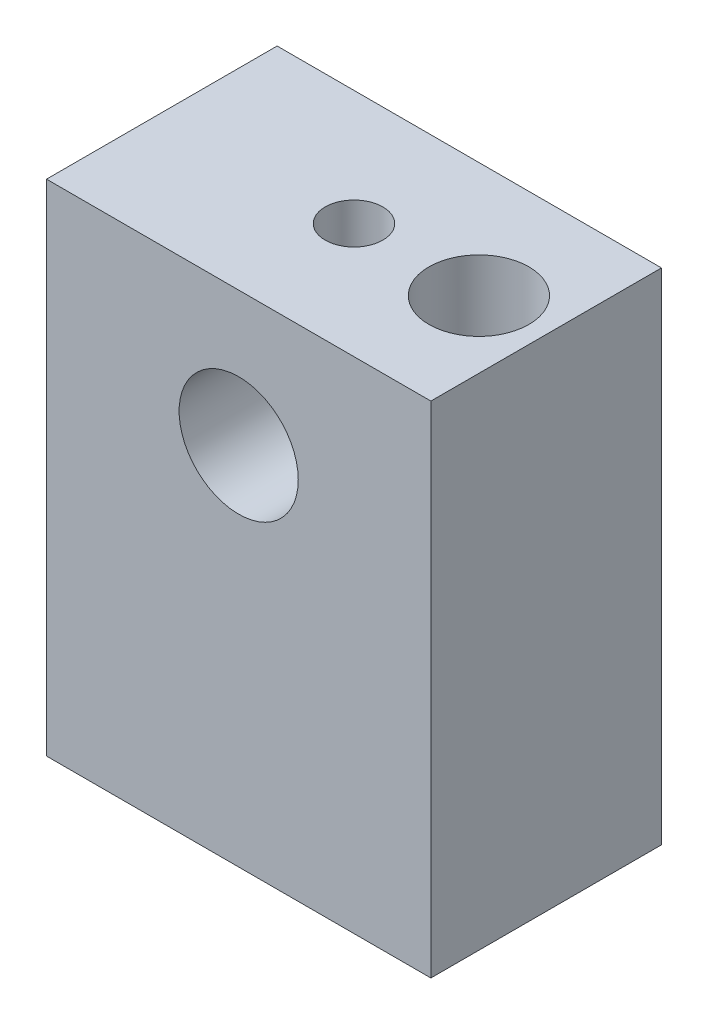
SolidWorks part; units mm, degrees
material "Brass"
ref_plane "Front Plane" through (0, 0, 0) normal (0, 0, 1) x (1, 0, 0)
ref_plane "Top Plane" through (0, 0, 0) normal (0, 1, 0) x (1, 0, 0)
ref_plane "Right Plane" through (0, 0, 0) normal (1, 0, 0) x (0, 0, -1)
sketch "Sketch1" plane through (0, 0, 0) normal (0, 0, 1) x (1, 0, 0)
  line L0 (-10, 0) -> (10, 0)
  line L1 (10, 0) -> (10, 26)
  line L2 (10, 26) -> (-10, 26)
  line L3 (-10, 26) -> (-10, 0)
  dimension "D1" = 20
  dimension "D2" = 26
  dimension "D3" = 10
extrude "Boss-Extrude1" add sketch "Sketch1" along normal blind 12
sketch "Sketch2" plane through (0, 0, 0) normal (0, 0, 1) x (1, 0, 0)
  circle A0 centre (0, 19) radius 3.1
  dimension "D2" = 6.2
  dimension "D1" = 19
extrude "Cut-Extrude1" cut sketch "Sketch2" against normal mid plane 80
sketch "Sketch3" plane through (0, 0, 0) normal (0, 1, 0) x (1, 0, 0)
  circle A0 centre (6.5, -6) radius 2.6
  circle A1 centre (0, -6) radius 1.5
  dimension "D3" = 5.2
  dimension "D5" = 3
  dimension "D1" = 6.5
  dimension "D2" = 6
  dimension "D4" = 6
extrude "Cut-Extrude2" cut sketch "Sketch3" against normal mid plane 80
ref_plane "Plane1" through (0, 19, 0) normal (0, 1, 0) x (1, 0, 0)
ref_axis "Axis1" through (0, 19, -0.6) along (0, 0, 1)
